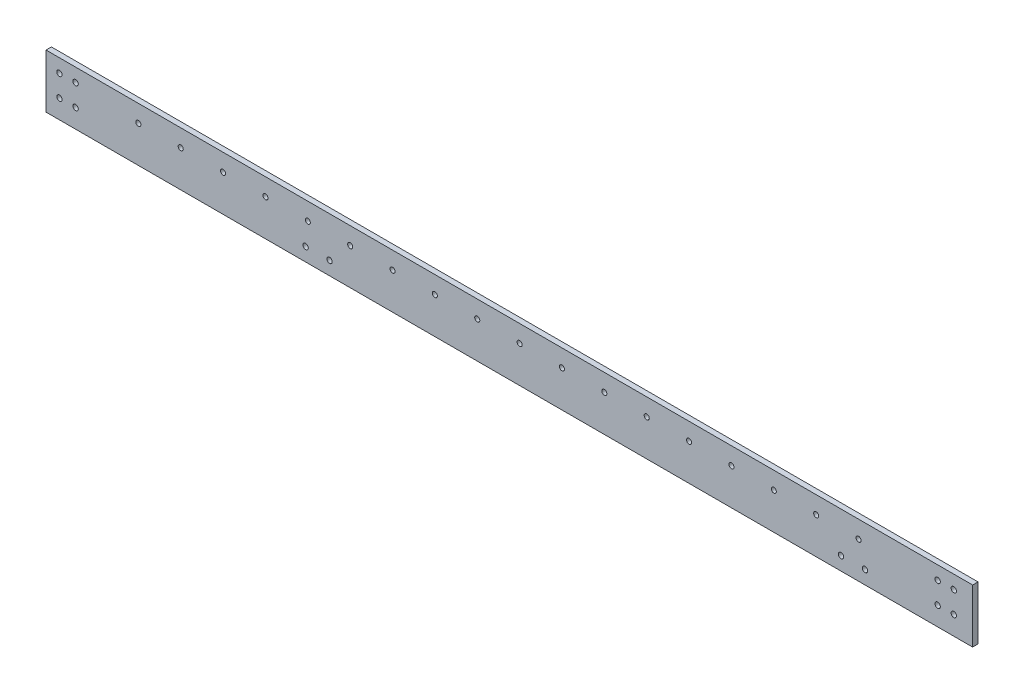
SolidWorks part; units mm, degrees
ref_plane "Front Plane" through (0, 0, 0) normal (0, 0, 1) x (1, 0, 0)
ref_plane "Top Plane" through (0, 0, 0) normal (0, 1, 0) x (1, 0, 0)
ref_plane "Right Plane" through (0, 0, 0) normal (1, 0, 0) x (0, 0, -1)
sketch "Sketch1" plane through (0, 0, 0) normal (1, 0, 0) x (0, 0, -1)
  line L0 (0, 0) -> (-3.175, 0)
  line L3 (-3.175, 0) -> (-3.175, 31.75)
  line L4 (-3.175, 31.75) -> (0, 31.75)
  line L5 (0, 31.75) -> (0, 0)
  dimension "LHeight" = 31.75
  dimension "LMaterialThickness" = 3.175
extrude "Boss-Extrude1" add sketch "Sketch1" along normal blind 546.825
sketch "SideHoles-Sketch4" plane through (0, 0, 3.175) normal (0, 0, 1) x (1, 0, 0)
  line L1 (546.825, 31.75) -> (546.825, 0) construction
  line L2 (0, 31.75) -> (0, 0) construction
  line L3 (546.825, 31.75) -> (0, 31.75) construction
  line L4 (546.825, 0) -> (0, 0) construction
  line L5 (546.825, 31.75) -> (0, 31.75) construction
  line L6 (0, 31.75) -> (0, 0) construction
  line L7 (546.825, 31.75) -> (546.825, 0) construction
  circle A1 centre (7.9375, 23.8125) radius 1.5875
  circle A3 centre (526.1875, 23.8125) radius 1.5875
  circle A4 centre (17.4625, 23.8125) radius 1.5875
  circle A5 centre (535.7125, 23.8125) radius 1.5875
  circle A6 centre (7.9375, 11.1125) radius 1.5875
  circle A7 centre (17.4625, 11.1125) radius 1.5875
  circle A8 centre (526.1875, 11.1125) radius 1.5875
  circle A9 centre (535.7125, 11.1125) radius 1.5875
  circle A10 centre (54.5, 21.525) radius 1.5
  circle A11 centre (79.5, 21.525) radius 1.5
  circle A12 centre (104.5, 21.525) radius 1.5
  circle A13 centre (129.5, 21.525) radius 1.5
  circle A14 centre (154.5, 21.525) radius 1.5
  circle A15 centre (179.5, 21.525) radius 1.5
  circle A16 centre (204.5, 21.525) radius 1.5
  circle A17 centre (229.5, 21.525) radius 1.5
  circle A18 centre (254.5, 21.525) radius 1.5
  circle A19 centre (279.5, 21.525) radius 1.5
  circle A20 centre (304.5, 21.525) radius 1.5
  circle A21 centre (329.5, 21.525) radius 1.5
  circle A22 centre (354.5, 21.525) radius 1.5
  circle A23 centre (379.5, 21.525) radius 1.5
  circle A24 centre (469.1875, 7.9375) radius 1.5875
  circle A25 centre (483.3125, 7.9375) radius 1.5875
  circle A26 centre (153.1875, 7.9375) radius 1.5875
  circle A27 centre (167.3125, 7.9375) radius 1.5875
  circle A29 centre (404.5, 21.525) radius 1.5
  circle A30 centre (429.5, 21.525) radius 1.5
  circle A31 centre (454.5, 21.525) radius 1.5
  circle A32 centre (479.5, 21.525) radius 1.5
  dimension "D2" = 3.175
  dimension "D10" = 3
  dimension "D14" = 3.175
  dimension "D4" = 7.9375
  dimension "D3" = 11.1125
  dimension "D5" = 20.6375
  dimension "D1" = 7.9375
  dimension "D6" = 17.4625
  dimension "D7" = 11.1125
  dimension "D9" = 10.225
  dimension "D8" = 54.5
  dimension "D12" = 25
  dimension "D15" = 7.9375
  dimension "D16" = 14.125
  dimension "D13" = 14.125
  dimension "D17" = 77.6375
  dimension "D18" = 316
  dimension "D11" = 18
extrude "SideHoles-Cut-Extrude3" cut sketch "SideHoles-Sketch4" against normal through all
equation "\"MidSideRailHeight\"= 1.25in"
equation "\"RailThickness\"= .125in'Spec"
equation "\"SideRailHoleY1FromEdge\"= \"HoleOffsetFromEdge\""
equation "\"SideRailHoleX1FromSide\"= \"HoleOffsetFromSide\""
equation "\"MidSideRailLength\"= \"SideRailLength\" - \"RailThickness\"'Equals 546.825 => MidSideRail buts up against MidBackRail"
equation "\"VSWidth\"= 1.25in'Spec"
equation "\"HoleOffsetFromEdge\"= \"RailThickness\" * 2.5"
equation "\"HoleOffsetFromSide\"= \"RailThickness\" * 3.5"
equation "\"SideRailHoleX2FromSide\"= \"VSWidth\" - \"HoleOffsetFromEdge\" - \"RailThickness\"'Equals 20.6375"
equation "\"FasteningHoleDiameter\"= .125in"
equation "\"StepperWidth\"= 42mm'Spec"
equation "\"D2@SideHoles-Sketch4\"=\"FasteningHoleDiameter\""
equation "\"LHeight@Sketch1\"=\"MidSideRailHeight\""
equation "\"LMaterialThickness@Sketch1\"=\"RailThickness\""
equation "\"D1@Boss-Extrude1\"=\"MidSideRailLength\""
equation "\"D4@SideHoles-Sketch4\"=\"SideRailHoleY1FromEdge\""
equation "\"D3@SideHoles-Sketch4\"=\"SideRailHoleX1FromSide\" "
equation "\"D5@SideHoles-Sketch4\"=\"SideRailHoleX2FromSide\" "
equation "\"D1@SideHoles-Sketch4\"=\"SideRailHoleX1FromSide\" -\"RailThickness\""
equation "\"D6@SideHoles-Sketch4\"=\"SideRailHoleX2FromSide\"-\"RailThickness\""
equation "\"LinearRailXMountHole\"= \"StepperWidth\" + \"LinearRailFirstHoleOffsetFromEdge\""
equation "\"D9@SideHoles-Sketch4\"=\"V6.3 GantryMiddleToToTopOfMidSideRail\""
equation "\"D8@SideHoles-Sketch4\"=\"LinearRailXMountHole\""
equation "\"LinearRailHoleDistance\"= 25mm'Spec"
equation "\"D12@SideHoles-Sketch4\"=\"LinearRailHoleDistance\""
equation "\"SideRailLength\"= 550mm"
equation "\"LinearRailFirstHoleOffsetFromEdge\"= 12.5mm'Spec"
equation "\"D7@SideHoles-Sketch4\"=\"HoleOffsetFromSide\""
equation "\"DistanceFromBedFrontToFirstLeftStepperHole\"= \"LeadScrewNutPadSize\" + 10mm'Equals 34"
equation "\"BeltTensionerDepth\"= \"BeltTensionerBackWallThickness\" + \"BeltTensionerInnerDepth\"'Equals 23.4"
equation "\"20TGT2PulleyDiameter\"= 17.9mm'Spec"
equation "\"BeltTensionerSpaceBetweenPulleyAndWall\"= 1.5mm"
equation "\"BeltTensionerBackWallThickness\"= 4mm"
equation "\"BeltTensionerInnerDepth\"= \"20TGT2PulleyDiameter\" + \"BeltTensionerSpaceBetweenPulleyAndWall\""
equation "\"DistanceFromFrontSideToBedFront\"= \"RailThickness\" + \"BeltTensionerDepth\" + 10mm'Equals 36.575"
equation "\"DistanceBetweenFrontToBackStepperHoles\"= \"BedLength\" - \"DistanceFromBedFrontToFirstLeftStepperHole\"'Equals 316"
equation "\"BedLength\"= \"BedInnerSquareLength\" + \"BedLWidth\" * 2 - \"BedOverlap\" * 2 + \"BedIncreasedByLength\"'Equals 350"
equation "\"BedOverlap\"= 20mm"
equation "\"BedThirdSize\"= 70mm"
equation "\"BedInnerSquareWidth\"= \"BedThirdSize\" * 3'Equals 210"
equation "\"BedLWidth\"= \"BedThirdSize\" + \"BedOverlap\"'Equals 90"
equation "\"BedIncreasedByLength\"= 0mm"
equation "\"LM8UUDiameter\"= 15mm"
equation "\"RodStabilizerDepth\"= \"LM8UUDiameter\" * 2"
equation "\"D14@SideHoles-Sketch4\"= \"FasteningHoleDiameter\""
equation "\"D15@SideHoles-Sketch4\"= \"HoleOffsetFromEdge\""
equation "\"D16@SideHoles-Sketch4\"=\"RodStabilizerDepth\" - \"HoleOffsetFromEdge\" * 2"
equation "\"BedInnerSquareLength\"= \"BedInnerSquareWidth\""
equation "\"GABMidWallHeight\"= 28mm'Must equal 28 or changes alignment"
equation "\"20TGT2PulleyWidth\"= 8.7mm'The STL of the Pulley in the diagram is a bit larger"
equation "\"GABMidShortRiserHeight\"= \"GABMidWallHeight\" / 2 - \"20TGT2PulleyWidth\"'Equals 5.3"
equation "\"GABUpperHeight\"= 6mm"
equation "\"GABLowerHeight\"= 3mm"
equation "\"GABRiserBossOffset\"= 0.8mm'Aligns Pulleys"
equation "\"GABHeight\"= \"GABLowerHeight\" + \"GABMidWallHeight\" + \"GABUpperHeight\""
equation "\"StepperShaftLength\"= 24mm'Pulley will be attached to the end"
equation "\"V6.1 FromGantryPulleyToGantryMiddle\"= \"GABHeight\" / 2 - \"GABMidShortRiserHeight\" - \"GABLowerHeight\" + \"GABRiserBossOffset\" / 2"
equation "\"V6.2 GantryMiddleToTopOfMidBackRail\"= \"StepperShaftLength\" - \"V6.1 FromGantryPulleyToGantryMiddle\""
equation "\"V6.3 GantryMiddleToToTopOfMidSideRail\"= \"V6.2 GantryMiddleToTopOfMidBackRail\" - \"RailThickness\""
equation "\"DistanceFromFrontSideToFirstLeftStabilizerMountingHole\"= \"DistanceFromFrontSideToFirstLeftStepperHole\" + \"RodStabilizerDepth\" / 2 - \"HoleOffsetFromEdge\"'Equals 77.6375"
equation "\"DistanceFromFrontSideToFirstLeftStepperHole\"= \"DistanceFromFrontSideToBedFront\" + \"DistanceFromBedFrontToFirstLeftStepperHole\"'Equals 70.575"
equation "\"D13@SideHoles-Sketch4\"=\"RodStabilizerDepth\" - \"HoleOffsetFromEdge\" * 2"
equation "\"LeadScrewNutMountingHoleFlangeDiameter\"= 22mm'Spec"
equation "\"LeadScrewNutPadSize\"= \"LeadScrewNutMountingHoleFlangeDiameter\" + 2mm'Equals 24"
equation "\"D17@SideHoles-Sketch4\"=\"DistanceFromFrontSideToFirstLeftStabilizerMountingHole\""
equation "\"D18@SideHoles-Sketch4\"=\"DistanceBetweenFrontToBackStepperHoles\""
